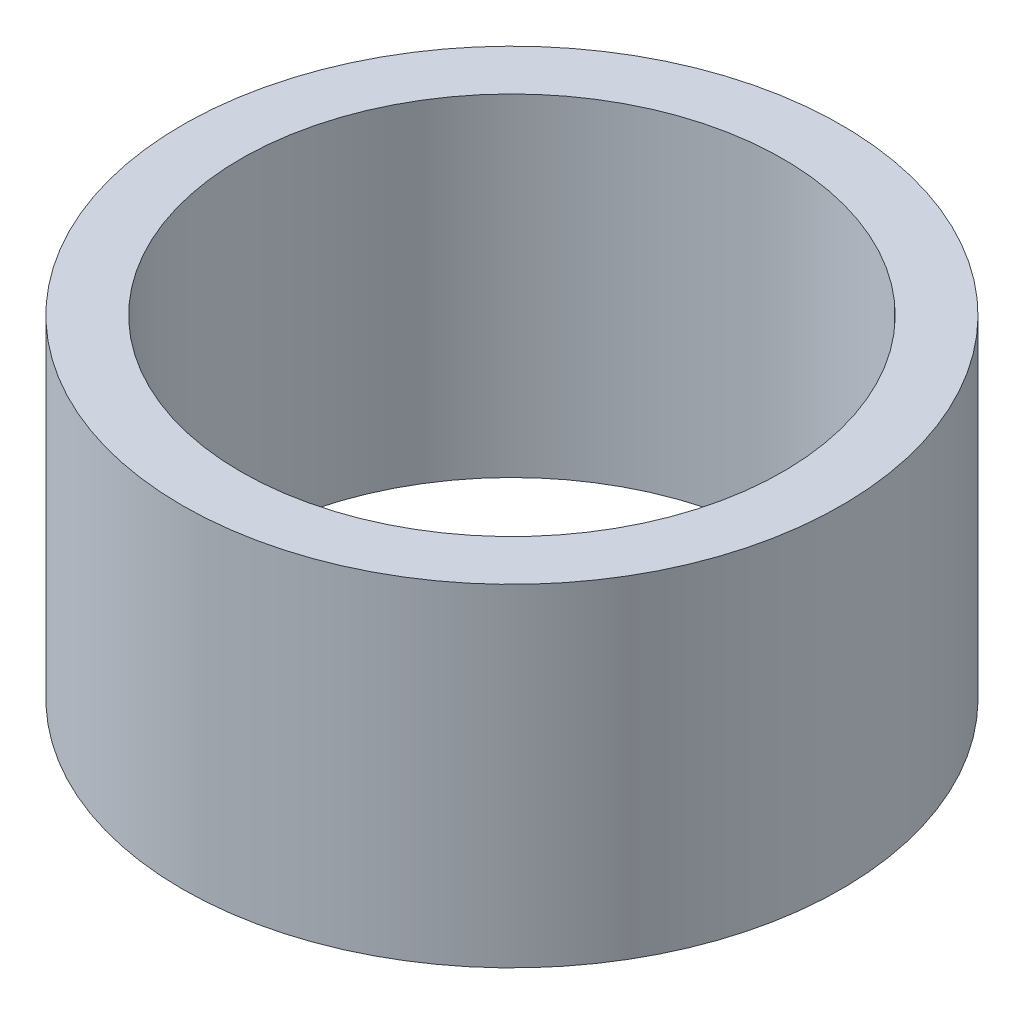
SolidWorks part; units mm, degrees
ref_plane "Front Plane" through (0, 0, 0) normal (0, 0, 1) x (1, 0, 0)
ref_plane "Top Plane" through (0, 0, 0) normal (0, 1, 0) x (1, 0, 0)
ref_plane "Right Plane" through (0, 0, 0) normal (1, 0, 0) x (0, 0, -1)
sketch "Sketch1" plane through (0, 0, 0) normal (0, 1, 0) x (1, 0, 0)
  circle A0 centre (0, 0) radius 3.2639
  circle A1 centre (0, 0) radius 3.9688
  dimension "D1" = 6.5278
  dimension "D2" = 7.9375
extrude "Boss-Extrude1" add sketch "Sketch1" along normal blind 4
